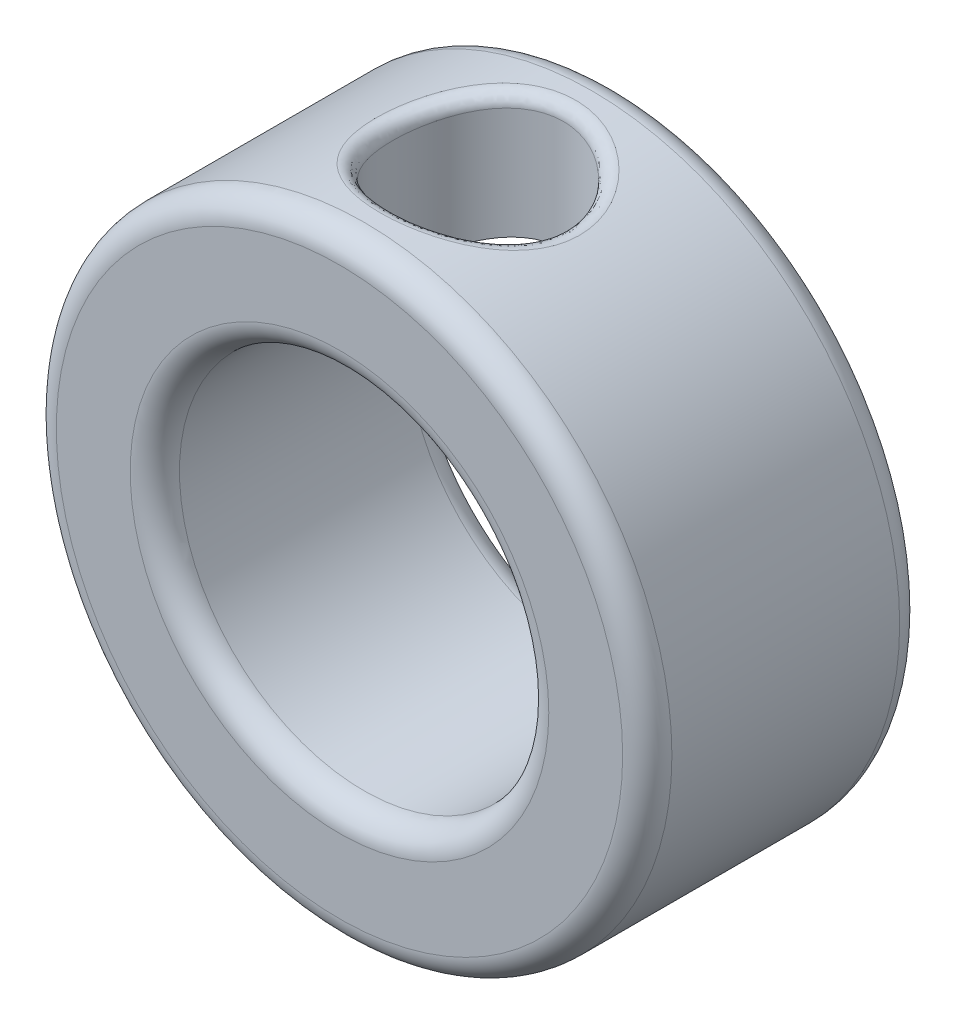
SolidWorks part; units mm, degrees
ref_plane "Front Plane" through (0, 0, 0) normal (0, 0, 1) x (1, 0, 0)
ref_plane "Top Plane" through (0, 0, 0) normal (0, 1, 0) x (1, 0, 0)
ref_plane "Right Plane" through (0, 0, 0) normal (1, 0, 0) x (0, 0, -1)
sketch "Sketch1" plane through (0, 0, 0) normal (0, 0, 1) x (1, 0, 0)
  circle A0 centre (0, 0) radius 9.525
  circle A1 centre (0, 0) radius 15.875
  dimension "D1" = 19.05
  dimension "D2" = 31.75
extrude "Boss-Extrude1" add sketch "Sketch1" along normal blind 7.1437 and the other way blind 7.1437
fillet "Fillet1" radius 1.27 4 edges at (15.875, 0, -7.1437) (9.525, 0, -7.1437) (15.875, 0, 7.1437) (9.525, 0, 7.1437)
sketch "Sketch3" plane through (0, 0, 0) normal (0, 1, 0) x (1, 0, 0)
  circle A0 centre (0, 0) radius 4.4028
  dimension "D1" = 8.8055
extrude "Cut-Extrude1" cut sketch "Sketch3" along normal through all
fillet "Fillet2" radius 0.635 1 edges at (-0.8272, 15.8534, 4.3243)
